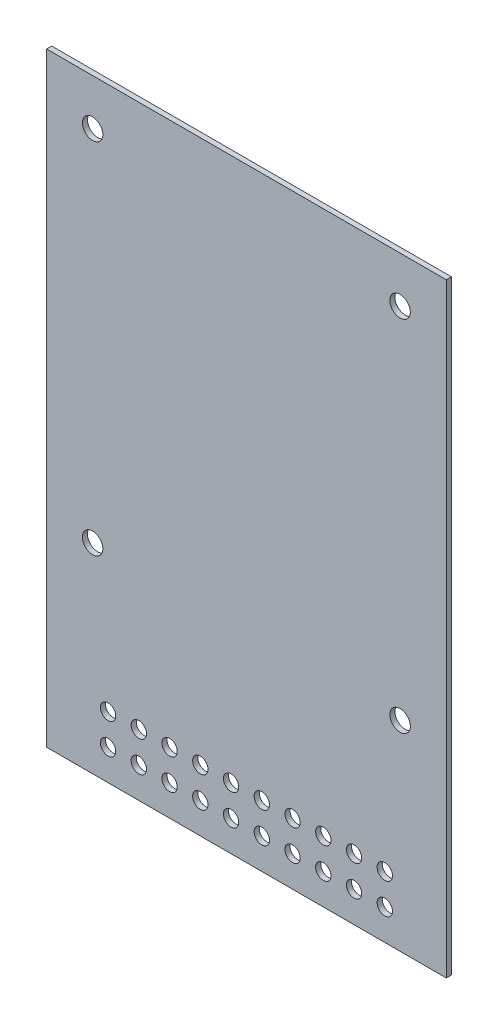
SolidWorks part; units mm, degrees
ref_plane "Front Plane" through (0, 0, 0) normal (0, 0, 1) x (1, 0, 0)
ref_plane "Top Plane" through (0, 0, 0) normal (0, 1, 0) x (1, 0, 0)
ref_plane "Right Plane" through (0, 0, 0) normal (1, 0, 0) x (0, 0, -1)
sketch "Sketch1" plane through (0, 0, 0) normal (0, 0, 1) x (1, 0, 0)
  line L1 (0, 0) -> (78, 0)
  line L2 (0, 0) -> (0, 118)
  line L3 (0, 118) -> (78, 118)
  line L4 (78, 0) -> (78, 118)
  dimension "D1" = 78
  dimension "D2" = 118
extrude "Boss-Extrude1" add sketch "Sketch1" along normal blind 1
sketch "Sketch2" plane through (0, 0, 0) normal (0, 0, -1) x (-1, 0, 0)
  line L0 (-78, 0) -> (-78, 118) construction
  line L1 (0, 0) -> (-78, 0) construction
  circle A0 centre (-8.9804, 39.0168) radius 2
  circle A1 centre (-68.9804, 39.0168) radius 2
  circle A2 centre (-68.9804, 109.0168) radius 2
  circle A3 centre (-8.9804, 109.0168) radius 2
  circle A4 centre (-66, 12) radius 1.5
  circle A5 centre (-60, 12) radius 1.5
  circle A6 centre (-54, 12) radius 1.5
  circle A7 centre (-48, 12) radius 1.5
  circle A8 centre (-42, 12) radius 1.5
  circle A9 centre (-36, 12) radius 1.5
  circle A10 centre (-30, 12) radius 1.5
  circle A11 centre (-24, 12) radius 1.5
  circle A12 centre (-18, 12) radius 1.5
  circle A13 centre (-12, 12) radius 1.5
  circle A14 centre (-60, 6) radius 1.5
  circle A15 centre (-54, 6) radius 1.5
  circle A16 centre (-48, 6) radius 1.5
  circle A17 centre (-42, 6) radius 1.5
  circle A18 centre (-36, 6) radius 1.5
  circle A19 centre (-30, 6) radius 1.5
  circle A20 centre (-24, 6) radius 1.5
  circle A21 centre (-18, 6) radius 1.5
  circle A22 centre (-12, 6) radius 1.5
  circle A23 centre (-66, 6) radius 1.5
  point P11 (-65.9033, 13.6948)
  point P12 (0, 0)
  point P53 (0, 0)
  point P54 (0, 0)
  point P57 (0, 0)
  point P58 (0, 0)
  dimension "D1" = 4
  dimension "D4" = 10
  dimension "D8" = 3
  dimension "D6" = 12
  dimension "D7" = 12
  dimension "D2" = 2
  dimension "D3" = 2
  dimension "D5" = 2
extrude "Cut-Extrude1" cut sketch "Sketch2" against normal through all
